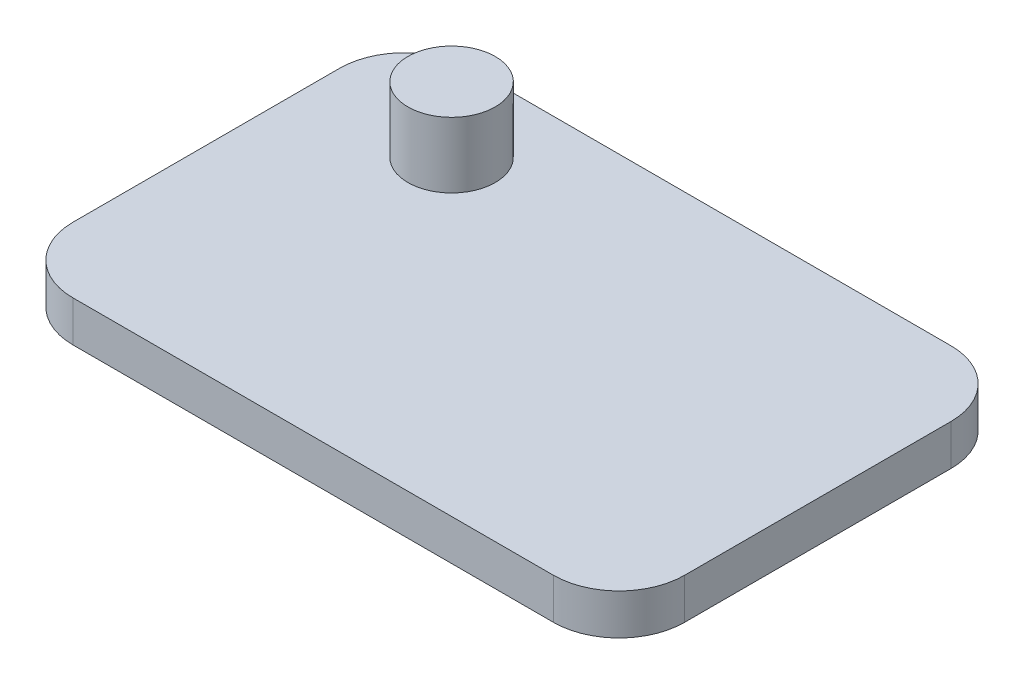
SolidWorks part; units mm, degrees
ref_plane "Front Plane" through (0, 0, 0) normal (0, 0, 1) x (1, 0, 0)
ref_plane "Top Plane" through (0, 0, 0) normal (0, 1, 0) x (1, 0, 0)
ref_plane "Right Plane" through (0, 0, 0) normal (1, 0, 0) x (0, 0, -1)
sketch "Sketch1" plane through (0, 0, 0) normal (0, 1, 0) x (1, 0, 0)
  line L0 (-228.5859, -146.0408) -> (228.5859, -146.0408)
  line L1 (-711.2, -462.28) -> (711.2, -462.28)
  line L2 (-711.2, -462.28) -> (-711.2, 462.28)
  line L3 (-711.2, 462.28) -> (711.2, 462.28)
  line L4 (711.2, -462.28) -> (711.2, 462.28)
  line L5 (-711.2, -462.28) -> (711.2, 462.28) construction
  line L6 (-711.2, 462.28) -> (711.2, -462.28) construction
  line L7 (323.4001, 159.41) -> (526.6001, 159.41)
  line L8 (323.4001, 159.41) -> (323.4001, 362.61)
  line L9 (323.4001, 362.61) -> (526.6001, 362.61)
  line L10 (526.6001, 159.41) -> (526.6001, 362.61)
  line L11 (323.4001, 159.41) -> (526.6001, 362.61) construction
  line L12 (323.4001, 362.61) -> (526.6001, 159.41) construction
  line L13 (171.0001, 210.21) -> (323.4001, 210.21)
  line L14 (171.0001, 210.21) -> (171.0001, 362.61)
  line L15 (171.0001, 362.61) -> (323.4001, 362.61)
  line L16 (323.4001, 210.21) -> (323.4001, 362.61)
  line L17 (171.0001, 210.21) -> (323.4001, 362.61) construction
  line L18 (171.0001, 362.61) -> (323.4001, 210.21) construction
  line L19 (-184.5999, 159.41) -> (171.0001, 159.41)
  line L20 (-184.5999, 159.41) -> (-184.5999, 362.61)
  line L21 (-184.5999, 362.61) -> (171.0001, 362.61)
  line L22 (171.0001, 159.41) -> (171.0001, 362.61)
  line L23 (-184.5999, 159.41) -> (171.0001, 362.61) construction
  line L24 (-184.5999, 362.61) -> (171.0001, 159.41) construction
  circle A0 centre (-401.5539, 261.01) radius 101.6
  circle A1 centre (-401.5539, 261.01) radius 76.2
  arc A2 (231.1257, -148.609) -> (-231.1257, -148.609) centre (0, -146.0408) cw
  arc A3 (228.5859, -146.0408) -> (231.1257, -148.609) centre (228.5859, -148.5808) cw
  arc A4 (-228.5859, -146.0408) -> (-231.1257, -148.609) centre (-228.5859, -148.5808) ccw
  point P0 (0, 0)
  point P8 (425.0001, 261.01)
  point P14 (247.2001, 286.41)
  point P15 (-6.7999, 261.01)
  point P29 (0, 0)
  point P30 (0, 0)
  point P31 (0, -133.5205)
  point P32 (0, 0)
  point P33 (0, 0)
  point P34 (0, 0)
  point P35 (0, 0)
  point P36 (0, 0)
  point P37 (0, 0)
  point P38 (0, 0)
  point P39 (502.787, 254.5837)
  point P40 (0, 0)
  point P41 (0, 0)
  point P42 (249.6016, 282.7154)
  point P43 (0, 0)
  point P44 (0, 0)
  point P45 (0, 0)
  point P46 (0, -148.5808)
  dimension "D6" = 2.54
  dimension "D7" = 203.2
  dimension "D10" = 152.4
  dimension "D11" = 231.14
  dimension "D1" = 1422.4
  dimension "D2" = 924.56
  dimension "D3" = 203.2
  dimension "D4" = 152.4
  dimension "D5" = 355.6
  dimension "D8" = 203.2
  dimension "D9" = 152.4
  dimension "D12" = 203.2
  dimension "D13" = 201.27
extrude "Boss-Extrude1" add sketch "Sketch1" against normal blind 94.8267 contours L1 L4 L3 L2
fillet "Fillet1" radius 152.4 4 edges at (-711.2, -47.4133, -462.28) (711.2, -47.4133, -462.28) (711.2, -47.4133, 462.28) (-711.2, -47.4133, 462.28)
extrude "Boss-Extrude2" add sketch "Sketch1<3>" along normal blind 152.4 contours A0
sketch "Sketch1<3>" plane through (0, 0, 0) normal (0, 1, 0) x (1, 0, 0) same geometry as "Sketch1"
sketch "Sketch3" plane through (0, 152.4, 0) normal (0, 1, 0) x (1, 0, 0)
  circle A0 centre (-401.5539, 261.01) radius 57.15
  circle A1 centre (-401.5539, 261.01) radius 101.6
  circle A2 centre (-401.5539, 261.01) radius 101.6
  dimension "D2" = 114.3
equation "\"A\"= 56"
equation "\"D1@Sketch1\"=\"A\""
equation "\"D2@Sketch1\"=\"A\"*.65"
equation "\"D3@Sketch1\"=\"A\"/7"
equation "\"D4@Sketch1\"=\"D3@Sketch1\"*.75"
equation "\"D5@Sketch1\"=\"D3@Sketch1\"*1.75"
equation "\"D1@Boss-Extrude1\"=\"A\"/15"
equation "\"B\"= 6"
equation "\"D1@Fillet1\"=\"B\""
equation "\"D8@Sketch1\"=\"D3@Sketch1\""
equation "\"D7@Sketch1\"=\"D8@Sketch1\""
equation "\"D9@Sketch1\"=\"D3@Sketch1\"*3/4"
equation "\"D10@Sketch1\"=\"D7@Sketch1\"*3/4"
equation "\"D11@Sketch1\"=\"D2@Sketch1\"/4"
equation "\"D12@Sketch1\"=8"
equation "\"D1@Boss-Extrude2\"=\"B\""
equation "\"D2@Sketch3\"=\"B\"*3/4"
